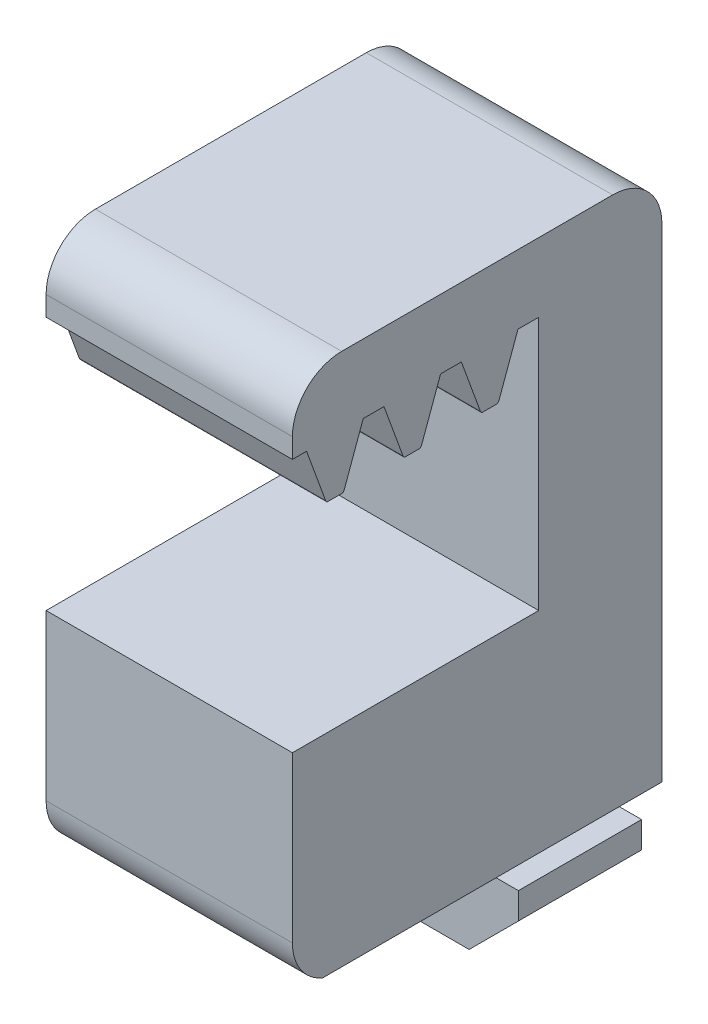
SolidWorks part; units mm, degrees
ref_plane "Front Plane" through (0, 0, 0) normal (0, 0, 1) x (1, 0, 0)
ref_plane "Top Plane" through (0, 0, 0) normal (0, 1, 0) x (1, 0, 0)
ref_plane "Right Plane" through (0, 0, 0) normal (1, 0, 0) x (0, 0, -1)
sketch "Sketch1" plane through (0, 0, 0) normal (1, 0, 0) x (0, 0, -1)
  line L0 (12.7, 0) -> (12.7, -6.096)
  line L1 (0, 27.686) -> (12.7, 27.686)
  line L2 (0, 27.686) -> (0, 21.336)
  line L3 (0, 21.336) -> (12.7, 21.336)
  line L5 (12.7, 27.686) -> (19.05, 27.686)
  line L6 (12.7, 21.336) -> (12.7, 11.43)
  line L7 (12.7, -6.096) -> (19.05, -6.096)
  line L8 (19.05, 27.686) -> (19.05, -6.096)
  line L9 (12.7, 11.43) -> (0, 11.43)
  line L11 (12.7, 0) -> (0, 0)
  line L12 (0, 11.43) -> (0, 0)
  dimension "D1" = 6.35
  dimension "D2" = 11.43
  dimension "D3" = 9.906
  dimension "D4" = 6.35
  dimension "D5" = 12.7
  dimension "D6" = 6.096
extrude "Boss-Extrude1" add sketch "Sketch1" along normal mid plane 12.7
sketch "Sketch2" plane through (6.35, 0, 0) normal (1, 0, 0) x (0, 0, -1)
  line L0 (3.6499, 24.13) -> (4.7203, 24.13) construction
  line L1 (5.6948, 21.4527) -> (4.7203, 24.13) construction
  line L2 (6.4261, 21.2852) -> (5.934, 21.2852) construction
  line L3 (7.6397, 24.13) -> (6.6653, 21.4527) construction
  line L4 (7.6397, 24.13) -> (8.7102, 24.13) construction
  line L5 (9.6846, 21.4527) -> (8.7102, 24.13) construction
  line L6 (10.4159, 21.2852) -> (9.9238, 21.2852) construction
  line L7 (11.6296, 24.13) -> (10.6551, 21.4527) construction
  line L8 (11.6296, 24.13) -> (12.7, 24.13) construction
  line L9 (3.6499, 24.13) -> (4.7203, 24.13)
  line L10 (5.6948, 21.4527) -> (4.7203, 24.13)
  line L11 (6.4261, 21.2852) -> (5.934, 21.2852)
  line L12 (7.6397, 24.13) -> (6.6653, 21.4527)
  line L13 (7.6397, 24.13) -> (8.7102, 24.13)
  line L14 (9.6846, 21.4527) -> (8.7102, 24.13)
  line L15 (10.4159, 21.2852) -> (9.9238, 21.2852)
  line L16 (11.6296, 24.13) -> (10.6551, 21.4527)
  line L17 (11.6296, 24.13) -> (12.7, 24.13)
  line L18 (12.7, 24.13) -> (12.7, 11.43)
  line L19 (12.7, 21.336) -> (12.7, 11.43) construction
  line L20 (12.7, 11.43) -> (3.6499, 11.43)
  line L21 (3.6499, 11.43) -> (3.6499, 24.13)
  line L22 (12.7, 11.43) -> (0, 11.43) construction
  arc A0 (5.6948, 21.4527) -> (5.934, 21.2852) centre (5.934, 21.5398) ccw construction
  arc A1 (6.4261, 21.2852) -> (6.6653, 21.4527) centre (6.4261, 21.5398) ccw construction
  arc A2 (9.6846, 21.4527) -> (9.9238, 21.2852) centre (9.9238, 21.5398) ccw construction
  arc A3 (10.4159, 21.2852) -> (10.6551, 21.4527) centre (10.4159, 21.5398) ccw construction
  arc A4 (5.6948, 21.4527) -> (5.934, 21.2852) centre (5.934, 21.5398) ccw
  arc A5 (6.4261, 21.2852) -> (6.6653, 21.4527) centre (6.4261, 21.5398) ccw
  arc A6 (9.6846, 21.4527) -> (9.9238, 21.2852) centre (9.9238, 21.5398) ccw
  arc A7 (10.4159, 21.2852) -> (10.6551, 21.4527) centre (10.4159, 21.5398) ccw
extrude "Cut-Extrude1" cut sketch "Sketch2" against normal through all
pattern_linear "LPattern1" count 10 spacing 3.9898 along (0, 0, 1) of "Cut-Extrude1"
sketch "Sketch3" plane through (0, 0, -19.05) normal (0, 0, -1) x (-1, 0, 0)
  line L0 (-6.35, -6.096) -> (-2.8393, -6.1)
  line L1 (2.8393, -6.1) -> (5.5, -3.4393) construction
  line L2 (5.5, -3.4393) -> (5.5, -1.8) construction
  line L3 (5.5, -1.8) -> (3.125, -1.8) construction
  line L4 (3.125, -1.8) -> (3.125, -1.455) construction
  line L5 (3.125, -1.455) -> (4.58, 0) construction
  line L6 (15.42, 0) -> (4.58, 0) construction
  line L7 (-4.58, 0) -> (-9.5, 0) construction
  line L8 (-3.125, -1.455) -> (-4.58, 0) construction
  line L9 (-3.125, -1.8) -> (-3.125, -1.455) construction
  line L10 (-5.5, -1.8) -> (-3.125, -1.8) construction
  line L11 (-5.5, -3.4393) -> (-5.5, -1.8) construction
  line L12 (-2.8393, -6.1) -> (-5.5, -3.4393) construction
  line L13 (2.8393, -6.1) -> (6.35, -6.096)
  line L15 (2.8393, -6.1) -> (5.5, -3.4393)
  line L16 (5.5, -3.4393) -> (5.5, -1.8)
  line L17 (5.5, -1.8) -> (3.125, -1.8)
  line L18 (3.125, -1.8) -> (3.125, -1.455)
  line L19 (3.125, -1.455) -> (4.58, 0)
  line L20 (15.42, 0) -> (4.58, 0)
  line L21 (-4.58, 0) -> (-9.5, 0)
  line L22 (-3.125, -1.455) -> (-4.58, 0)
  line L23 (-3.125, -1.8) -> (-3.125, -1.455)
  line L24 (-5.5, -1.8) -> (-3.125, -1.8)
  line L25 (-5.5, -3.4393) -> (-5.5, -1.8)
  line L26 (-2.8393, -6.1) -> (-5.5, -3.4393)
  line L29 (-9.5, 0) -> (-6.35, -6.096)
  line L32 (6.35, -6.096) -> (15.42, 0)
extrude "Cut-Extrude2" cut sketch "Sketch3" against normal through all
fillet "Fillet1" radius 2.54 3 edges at (0, 0, 0) (0, 27.686, 0) (0, 27.686, -19.05)
sketch "Sketch5" plane through (0, 0, -19.05) normal (0, 0, -1) x (-1, 0, 0)
  line L0 (6.35, 0) -> (4.58, 0) construction
  line L1 (4.58, 0) -> (3.125, -1.455) construction
  line L2 (3.125, -1.455) -> (3.125, -1.8) construction
  line L3 (3.125, -1.8) -> (5.5, -1.8) construction
  line L4 (5.5, -1.8) -> (5.5, -3.4393) construction
  line L5 (5.5, -3.4393) -> (2.8433, -6.096) construction
  line L6 (-2.8433, -6.096) -> (2.8433, -6.096) construction
  line L7 (-2.8433, -6.096) -> (-5.5, -3.4393) construction
  line L8 (-5.5, -3.4393) -> (-5.5, -1.8) construction
  line L9 (-5.5, -1.8) -> (-3.125, -1.8) construction
  line L10 (-3.125, -1.8) -> (-3.125, -1.455) construction
  line L11 (-3.125, -1.455) -> (-4.58, 0) construction
  line L12 (-4.58, 0) -> (-6.35, 0) construction
  line L13 (6.35, 0) -> (4.58, 0)
  line L14 (4.58, 0) -> (3.125, -1.455)
  line L15 (3.125, -1.455) -> (3.125, -1.8)
  line L16 (3.125, -1.8) -> (5.5, -1.8)
  line L17 (5.5, -1.8) -> (5.5, -3.4393)
  line L18 (5.5, -3.4393) -> (2.8433, -6.096)
  line L19 (-2.8433, -6.096) -> (2.8433, -6.096)
  line L20 (-2.8433, -6.096) -> (-5.5, -3.4393)
  line L21 (-5.5, -3.4393) -> (-5.5, -1.8)
  line L22 (-5.5, -1.8) -> (-3.125, -1.8)
  line L23 (-3.125, -1.8) -> (-3.125, -1.455)
  line L24 (-3.125, -1.455) -> (-4.58, 0)
  line L25 (-4.58, 0) -> (-6.35, 0)
  line L26 (6.35, 0.1984) -> (4.4978, 0.1984)
  line L27 (4.4978, 0.1984) -> (2.9266, -1.3728)
  line L28 (2.9266, -1.3728) -> (2.9266, -1.9984)
  line L29 (2.9266, -1.9984) -> (5.3016, -1.9984)
  line L30 (5.3016, -1.9984) -> (5.3016, -3.3571)
  line L31 (5.3016, -3.3571) -> (2.7611, -5.8976)
  line L32 (-2.7611, -5.8976) -> (2.7611, -5.8976)
  line L33 (-2.7611, -5.8976) -> (-5.3016, -3.3571)
  line L34 (-5.3016, -3.3571) -> (-5.3016, -1.9984)
  line L35 (-5.3016, -1.9984) -> (-2.9266, -1.9984)
  line L36 (-2.9266, -1.9984) -> (-2.9266, -1.3728)
  line L37 (-2.9266, -1.3728) -> (-4.4978, 0.1984)
  line L38 (-4.4978, 0.1984) -> (-6.35, 0.1984)
  line L39 (6.35, 0) -> (6.35, 0.1984)
  line L40 (-6.35, 0) -> (-6.35, 0.1984)
  dimension "D1" = 0.1984
extrude "Cut-Extrude3" cut sketch "Sketch5" against normal through all
sketch "Sketch6" plane through (6.35, 0, 0) normal (1, 0, 0) x (0, 0, -1)
  line L0 (12.7, 24.13) -> (12.7, 11.43) construction
  line L1 (0, 11.43) -> (12.7, 11.43)
  line L2 (0, 11.43) -> (0, 11.0331)
  line L3 (0, 11.0331) -> (12.7, 11.0331)
  line L4 (12.7, 11.43) -> (12.7, 11.0331)
  point P5 (0, 0)
  dimension "D1" = 0.3969
extrude "Cut-Extrude4" cut sketch "Sketch6" against normal through all
